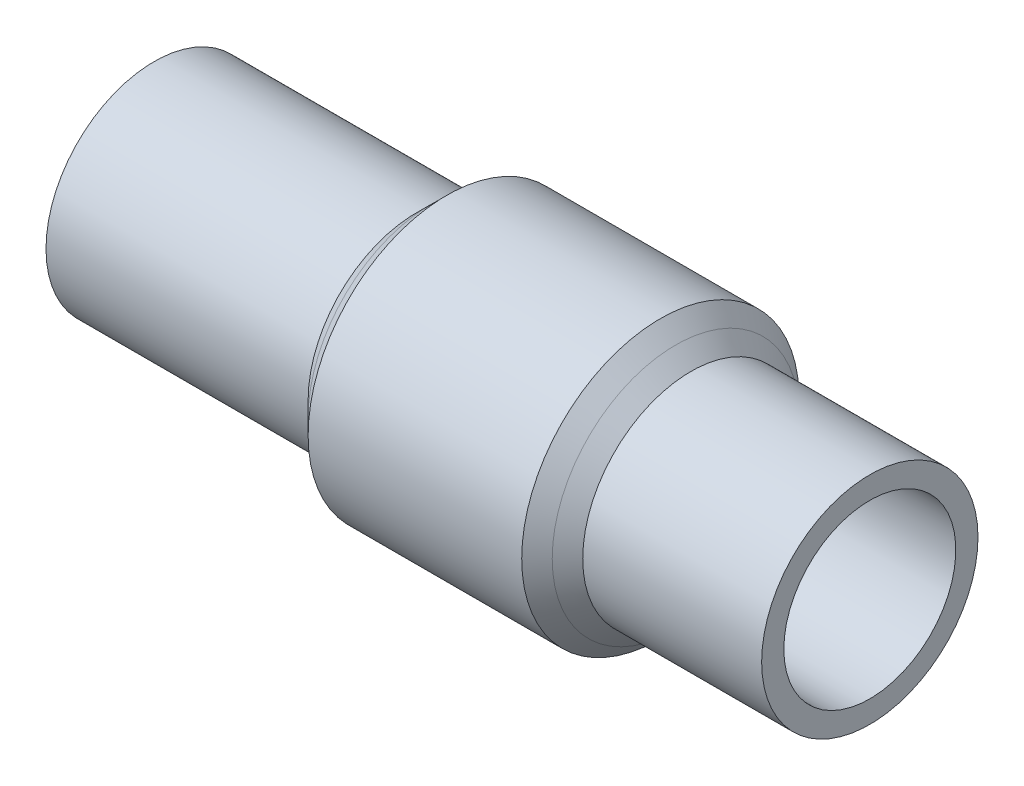
SolidWorks part; units mm, degrees
ref_plane "Front Plane" through (0, 0, 0) normal (0, 0, 1) x (1, 0, 0)
ref_plane "Top Plane" through (0, 0, 0) normal (0, 1, 0) x (1, 0, 0)
ref_plane "Right Plane" through (0, 0, 0) normal (1, 0, 0) x (0, 0, -1)
sketch "Sketch1" plane through (0, 0, 0) normal (0, 1, 0) x (1, 0, 0)
  line L0 (-11.4, 3.1) -> (11.4, 3.1)
  line L1 (-11.4, 3.1) -> (-11.4, 3.9)
  line L2 (-11.4, 3.9) -> (-4.4, 3.9)
  line L3 (-4.4, 3.9) -> (-4.4, 5)
  line L4 (-4.4, 5) -> (4.4, 5)
  line L5 (4.4, 5) -> (4.4, 3.9)
  line L6 (4.4, 3.9) -> (11.4, 3.9)
  line L7 (11.4, 3.9) -> (11.4, 3.1)
  line L8 (-11.4, 3.1) -> (-11.4, 0) construction
  line L9 (-11.4, 0) -> (11.4, 0) construction
  line L10 (11.4, 0) -> (11.4, 3.1) construction
  point P2 (0, 3.1)
  point P3 (0, 5)
  dimension "D1" = 3.1
  dimension "D2" = 7
  dimension "D3" = 3.9
  dimension "D4" = 8.8
  dimension "D5" = 5
revolve "Revolve1" add sketch "Sketch1" angle 360 about L9
sketch "Sketch6" plane through (11.4, 0, 0) normal (1, 0, 0) x (0, 0, -1)
  line L0 (0, 0) -> (3.9, 0) construction
  line L1 (2.6, 0) -> (3.0772, -0.375)
  line L2 (2.6, 0) -> (3.0772, 0.375)
  circle A0 centre (0, 0) radius 3.9 construction
  circle A1 centre (0, 0) radius 3.1 construction
  arc A2 (3.0772, 0.375) -> (3.0772, -0.375) centre (0, 0) cw
  point P10 (3.1, 0)
  dimension "D2" = 0.75
  dimension "D1" = 0.5
extrude "Boss-Extrude1" [suppressed] add sketch "Sketch6" against normal up to surface (22.8 mm away)
chamfer "Chamfer6" [suppressed] distance 1 distance2 0.2
pattern_circular "CirPattern2" [suppressed] count 24 over 360 about axis through (-11.4, 0, 0) along (1, 0, 0) of bodies 108
chamfer "Chamfer7" [suppressed] distance 1 angle 45
chamfer "Chamfer8" distance 0.55 angle 45 4 edges at (-4.4, 0, 5) (-4.4, 0, 3.9) (4.4, 0, 5) (4.4, 0, 3.9)
sketch "Sketch8" plane through (-11.4, 0, 0) normal (-1, 0, 0) x (0, 0, 1)
  circle A0 centre (0, 0) radius 3.9
extrude "Boss-Extrude3" add sketch "Sketch8" along normal blind 3
